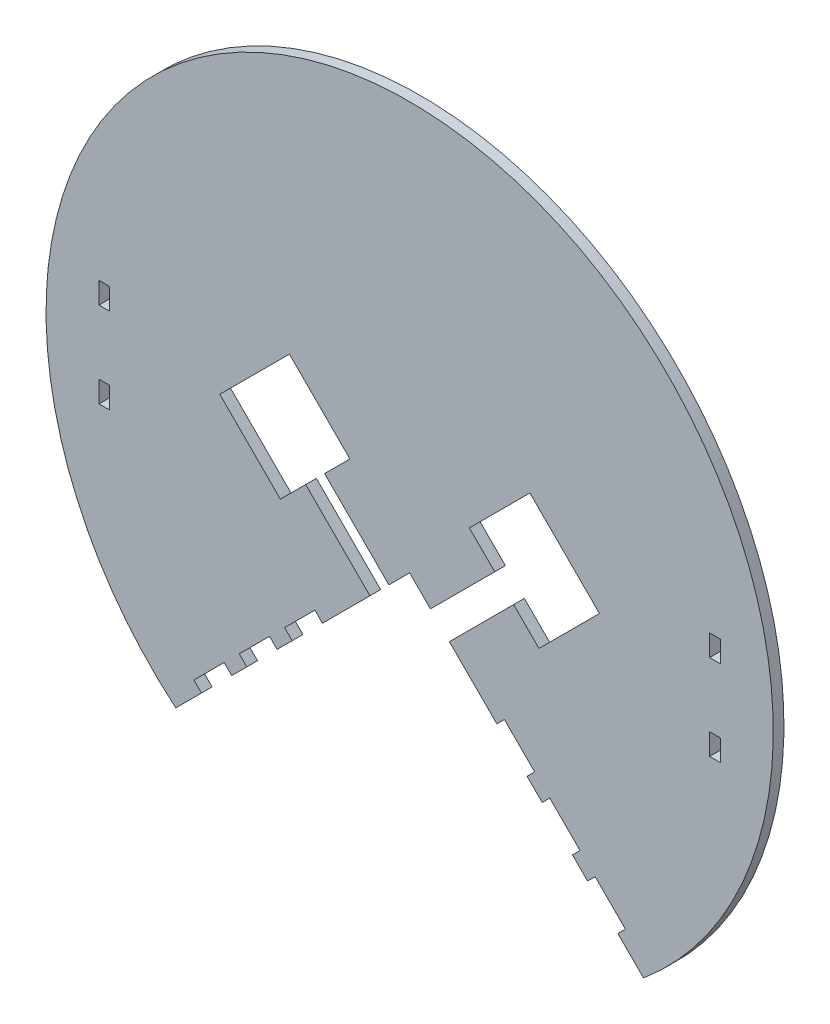
SolidWorks part; units mm, degrees
ref_plane "Front Plane" through (0, 0, 0) normal (0, 0, 1) x (1, 0, 0)
ref_plane "Top Plane" through (0, 0, 0) normal (0, 1, 0) x (1, 0, 0)
ref_plane "Right Plane" through (0, 0, 0) normal (1, 0, 0) x (0, 0, -1)
sketch "Sketch1" plane through (0, 0, 0) normal (0, 0, 1) x (1, 0, 0)
  circle A0 centre (0, 0) radius 215.9
  arc A1 (209.8384, 50.8) -> (-209.8384, 50.8) centre (0, 0) ccw construction
extrude "Boss-Extrude1" add sketch "Sketch1" along normal blind 6.35 contours A0
sketch "Sketch2" plane through (0, 0, 0) normal (0, 0, -1) x (-1, 0, 0)
  line L0 (0, -26.4411) -> (138.8703, -165.3114)
  line L2 (0, -26.4411) -> (-138.8703, -165.3114)
  line L3 (-139.4438, -165.8849) -> (0, -26.4411) construction
  line L4 (0, 0) -> (0, -240.5018) construction
  arc A4 (-138.8703, -165.3114) -> (138.8703, -165.3114) centre (0, 0) ccw
  circle A5 centre (0, 0) radius 215.9 construction
  dimension "D1" = 90
extrude "Cut-Extrude1" cut sketch "Sketch2" against normal through all
sketch "Sketch3" plane through (0, 0, 6.35) normal (0, 0, 1) x (1, 0, 0)
  line L0 (71.393, 50.3401) -> (112.7022, 9.0309)
  line L1 (71.393, 50.3401) -> (35.472, 14.4191)
  line L2 (112.7022, 9.0309) -> (76.7812, -26.8901)
  line L3 (35.472, 14.4191) -> (76.7812, -26.8901)
  line L4 (76.7812, -26.8901) -> (72.2911, -22.4) construction
  line L5 (97.2507, 34.8885) -> (46.1575, -16.2046) construction
  line L6 (50.5139, -0.6229) -> (61.7393, -11.8482)
  line L7 (50.5139, -0.6229) -> (12.3479, -38.7889)
  line L8 (61.7393, -11.8482) -> (23.5732, -50.0143)
  line L9 (12.3479, -38.7889) -> (23.5732, -50.0143)
  line L10 (88.68, 15.0926) -> (77.4547, 26.3179) construction
  line L11 (0, -26.4411) -> (138.8703, -165.3114) construction
  line M8 (0, -26.4411) -> (138.8703, -165.3114)
extrude "Cut-Extrude2" cut sketch "Sketch3" against normal through all contours L8 L6 L3 L7 M8 | L0 L5 L6 L3 L2 | L5 L0 L1 L3 region at (63.7598, 22.0523, 6.35) region at (84.4144, 1.3977, 6.35) region at (37.0436, -25.3186, 6.35)
mirror "Mirror1" about plane through (0, 0, 0) normal (1, 0, 0) of "Cut-Extrude2"
sketch "Sketch4" plane through (0, 0, 6.35) normal (0, 0, 1) x (1, 0, 0)
  line L0 (-178.0884, 19.05) -> (-178.0884, 31.75) construction
  line L1 (178.0884, -19.05) -> (184.4384, -19.05)
  line L2 (178.0884, -19.05) -> (178.0884, -31.75)
  line L3 (178.0884, -31.75) -> (184.4384, -31.75)
  line L4 (184.4384, -19.05) -> (184.4384, -31.75)
  line L5 (178.0884, 31.75) -> (184.4384, 31.75)
  line L6 (178.0884, 31.75) -> (178.0884, 19.05)
  line L7 (178.0884, 19.05) -> (184.4384, 19.05)
  line L8 (184.4384, 31.75) -> (184.4384, 19.05)
  line L9 (178.0884, -19.05) -> (184.4384, -19.05)
  line L10 (178.0884, -19.05) -> (178.0884, -31.75)
  line L11 (178.0884, -31.75) -> (184.4384, -31.75)
  line L12 (184.4384, -19.05) -> (184.4384, -31.75)
  line L13 (-184.4384, 31.75) -> (-178.0884, 31.75)
  line L14 (-184.4384, 31.75) -> (-184.4384, 19.05)
  line L15 (-184.4384, 19.05) -> (-178.0884, 19.05)
  line L16 (-178.0884, 31.75) -> (-178.0884, 19.05)
  line L18 (-184.4384, -19.05) -> (-178.0884, -19.05)
  line L19 (-184.4384, -19.05) -> (-184.4384, -31.75)
  line L20 (-184.4384, -31.75) -> (-178.0884, -31.75)
  line L21 (-178.0884, -19.05) -> (-178.0884, -31.75)
extrude "Cut-Extrude3" cut sketch "Sketch4" against normal through all contours L21 L18 L19 L20 | L8 L5 L6 L7 | L4 L1 L2 L3 | L14 L15 L16 L13 region at (181.2634, -25.4, 6.35) region at (181.2634, 25.4, 6.35) region at (-181.2634, -25.4, 6.35)
sketch "Sketch5" plane through (0, 0, 6.35) normal (0, 0, 1) x (1, 0, 0)
  line L0 (-128.1057, -145.5666) -> (-110.1452, -127.6061)
  line L1 (-110.1452, -127.6061) -> (-105.6551, -132.0962)
  line L2 (-138.8703, -165.3114) -> (-23.5732, -50.0143) construction
  line L3 (-105.6551, -132.0962) -> (-110.1452, -127.6061) construction
  line L4 (-105.6551, -132.0962) -> (-123.6156, -150.0567)
  line L5 (-128.1057, -145.5666) -> (-123.6156, -150.0567) construction
  line L6 (-123.6156, -150.0567) -> (-128.1057, -145.5666)
extrude "Cut-Extrude4" cut sketch "Sketch5" against normal blind 6.35
pattern_linear "LPattern1" count 3 spacing 38.1 along (0.7071, 0.7071, 0) of "Cut-Extrude4"
sketch "Sketch6" plane through (0, 0, 6.35) normal (0, 0, 1) x (1, 0, 0)
  line L0 (110.1452, -127.6061) -> (128.1057, -145.5666)
  line L1 (128.1057, -145.5666) -> (123.6156, -150.0567)
  line L2 (23.5732, -50.0143) -> (138.8703, -165.3114) construction
  line L3 (123.6156, -150.0567) -> (128.1057, -145.5666) construction
  line L4 (123.6156, -150.0567) -> (105.6551, -132.0962)
  line L5 (110.1452, -127.6061) -> (105.6551, -132.0962) construction
  line L6 (105.6551, -132.0962) -> (110.1452, -127.6061)
extrude "Cut-Extrude5" cut sketch "Sketch6" against normal blind 6.35
pattern_linear "LPattern2" count 3 spacing 38.1 along (-0.7071, 0.7071, 0) of "Cut-Extrude5"
